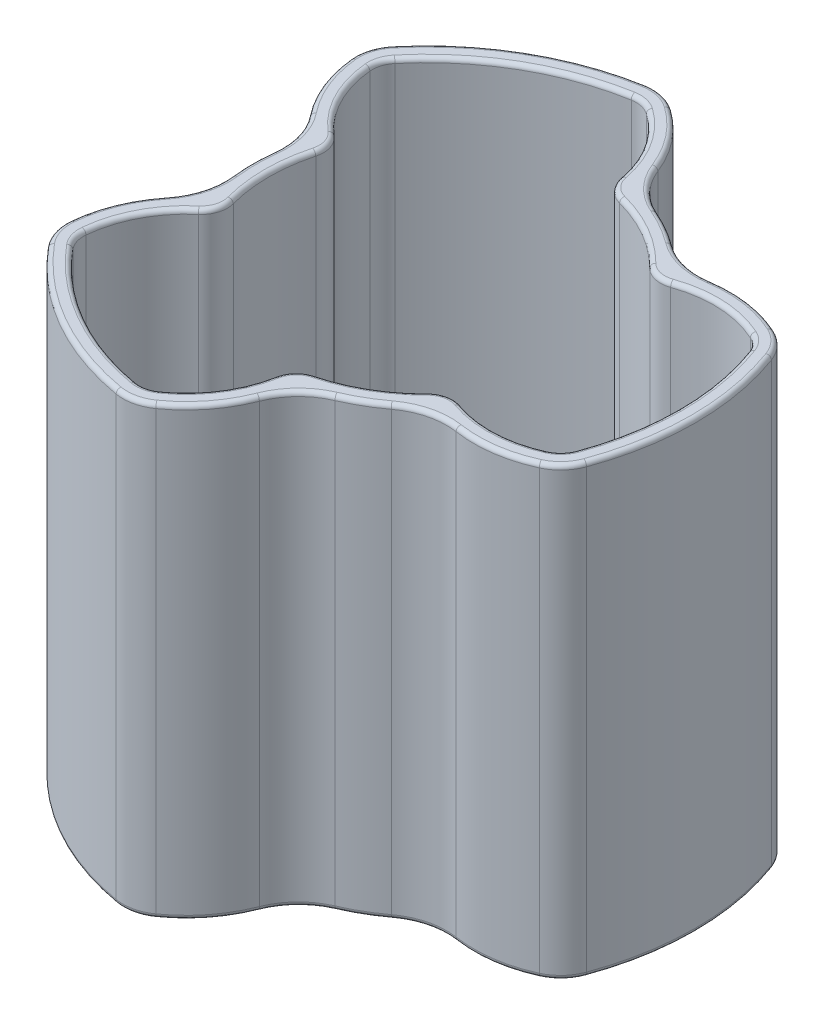
SolidWorks part; units mm, degrees
material "AISI 4340 Stal normalizowana"
ref_plane "Płaszczyzna XY" through (0, 0, 0) normal (0, 0, 1) x (1, 0, 0)
ref_plane "Płaszczyzna XZ" through (0, 0, 0) normal (0, 1, 0) x (1, 0, 0)
ref_plane "Płaszczyzna YZ" through (0, 0, 0) normal (1, 0, 0) x (0, 0, -1)
sketch "Szkic1" plane through (0, 0, 0) normal (0, 1, 0) x (1, 0, 0)
  line L0 (0, 0) -> (-10.15, -17.5803) construction
  line L1 (0, 0) -> (20.3, 0) construction
  arc A0 (28.3884, -12.454) -> (28.3884, 12.454) centre (0, 0) ccw
  arc A1 (26.7972, -11.0864) -> (26.7972, 11.0864) centre (0, 0) ccw
  arc A2 (14.2416, 11.3322) -> (2.6932, 17.9996) centre (0, 0) ccw
  arc A3 (14.7687, 13.7814) -> (4.5507, 19.6807) centre (0, 0) ccw
  circle A4 centre (0, 0) radius 20.3 construction
  arc A5 (26.7972, 11.0864) -> (14.2416, 11.3322) centre (20.3, 0) ccw
  arc A6 (28.3884, 12.454) -> (14.7687, 13.7814) centre (20.3, 0) ccw
  arc A7 (-3.7975, -28.7503) -> (2.6932, -17.9996) centre (-10.15, -17.5803) ccw
  arc A8 (-3.4087, -30.812) -> (4.5507, -19.6807) centre (-10.15, -17.5803) ccw
  arc A9 (-22.9997, 17.6639) -> (-16.9347, 6.6675) centre (-10.15, 17.5803) ccw
  arc A10 (-24.9796, 18.3581) -> (-19.3194, 5.8993) centre (-10.15, 17.5803) ccw
  arc A11 (-16.9347, 6.6675) -> (-16.9347, -6.6675) centre (0, 0) ccw
  arc A12 (-19.3194, 5.8993) -> (-19.3194, -5.8993) centre (0, 0) ccw
  arc A13 (4.5507, -19.6807) -> (14.7687, -13.7814) centre (0, 0) ccw
  arc A14 (2.6932, -17.9996) -> (14.2416, -11.3322) centre (0, 0) ccw
  arc A15 (-3.7975, 28.7503) -> (-22.9997, 17.6639) centre (0, 0) ccw
  arc A16 (-3.4087, 30.812) -> (-24.9796, 18.3581) centre (0, 0) ccw
  arc A17 (-24.9796, -18.3581) -> (-3.4087, -30.812) centre (0, 0) ccw
  arc A18 (-22.9997, -17.6639) -> (-3.7975, -28.7503) centre (0, 0) ccw
  arc A19 (-16.9347, -6.6675) -> (-22.9997, -17.6639) centre (-10.15, -17.5803) ccw
  arc A20 (-19.3194, -5.8993) -> (-24.9796, -18.3581) centre (-10.15, -17.5803) ccw
  arc A21 (4.5507, 19.6807) -> (-3.4087, 30.812) centre (-10.15, 17.5803) ccw
  arc A22 (2.6932, 17.9996) -> (-3.7975, 28.7503) centre (-10.15, 17.5803) ccw
  arc A23 (14.7687, -13.7814) -> (28.3884, -12.454) centre (20.3, 0) ccw
  arc A24 (14.2416, -11.3322) -> (26.7972, -11.0864) centre (20.3, 0) ccw
  point P19 (0, 0)
  dimension "D1" = 58
  dimension "D2" = 2
  dimension "D3" = 36.4
  dimension "D4" = 2
  dimension "D5" = 40.6
  dimension "D6" = 25.7
  dimension "D7" = 2
  dimension "D9" = 120
  dimension "D10" = 20.3
  dimension "D8" = 3
extrude "Dodanie-wyciągnięcie1" add sketch "Szkic1" along normal blind 44.5
extrude "Dodanie-wyciągnięcie2" add sketch "Szkic1<2>" against normal blind 7 contours A23 A0 A6 A3 A21 A16 A10 A12 A20 A17 A8 A13
sketch "Szkic1<2>" plane through (0, 0, 0) normal (0, 1, 0) x (1, 0, 0) same geometry as "Szkic1"
ref_plane "Płaszczyzna2" through (0, -7, 0) normal (0, -1, 0) x (-1, 0, 0)
sketch "Szkic2" plane through (0, -7, 0) normal (0, -1, 0) x (-1, 0, 0)
  line L0 (7.5, -12.9904) -> (0, 0)
  line L1 (0, 0) -> (-15, 0)
  circle A0 centre (0, 0) radius 15 construction
  circle A1 centre (-15, 0) radius 6.5
  circle A2 centre (7.5, 12.9904) radius 6.5
  circle A3 centre (7.5, -12.9904) radius 6.5
  point P12 (0, 0)
  dimension "D1" = 30
  dimension "D2" = 13
  dimension "D4" = 15
  dimension "D5" = 120
  dimension "D3" = 3
extrude "Wytnij-wyciągnięcie1" cut sketch "Szkic2" against normal blind 17 contours A1 | A3 | A2 region at (21.3162, -7, 0) region at (-10.6581, -7, 7.5204) region at (-7.5, -7, -12.9904)
fillet "Zaokrąglenie1" radius 3 12 edges at (14.2416, 22.25, -11.3322) (2.6932, 22.25, -17.9996) (-3.7975, 22.25, -28.7503) (-22.9997, 22.25, -17.6639) (-16.9347, 22.25, -6.6675) (-16.9347, 22.25, 6.6675) (-22.9997, 22.25, 17.6639) (-3.7975, 22.25, 28.7503) (2.6932, 22.25, 17.9996) (14.2416, 22.25, 11.3322) (26.7972, 22.25, 11.0864) (26.7972, 22.25, -11.0864)
fillet "Zaokrąglenie4" [suppressed] radius 2
chamfer "Sfazowanie2" distance 0.5 angle 45 3 edges at (15, 0, 6.5) (-7.5, 0, 19.4904) (-7.5, 0, -6.4904)
fillet "Zaokrąglenie8" radius 5 6 edges at (-24.9796, 18.75, -18.3581) (-24.9796, 18.75, 18.3581) (-3.4087, 18.75, 30.812) (-3.4087, 18.75, -30.812) (28.3884, 18.75, -12.454) (28.3884, 18.75, 12.454)
fillet "Zaokrąglenie9" radius 8 6 edges at (14.7687, 18.75, 13.7814) (4.5507, 18.75, 19.6807) (14.7687, 18.75, -13.7814) (4.5507, 18.75, -19.6807) (-19.3194, 18.75, -5.8993) (-19.3194, 18.75, 5.8993)
fillet "Zaokrąglenie5" radius 0.5 75 edges at (14.3638, 44.5, -12.0244) (20.8889, 44.5, -12.8365) (26.614, 44.5, -10.9872) (29, 44.5, 0) (26.614, 44.5, 10.9872) (20.8889, 44.5, 12.8365) (14.3638, 44.5, 12.0244) (9.1, 44.5, 15.7617) (3.2316, 44.5, 18.4516) (0.6723, 44.5, 24.5086) (-3.7918, 44.5, 28.542) (-14.5, 44.5, 25.1147) (-22.8222, 44.5, 17.5548) (-21.5612, 44.5, 11.6721) (-17.5953, 44.5, 6.4272) (-18.2, 44.5, 0) (-17.5953, 44.5, -6.4272) (-21.5612, 44.5, -11.6721) (-22.8222, 44.5, -17.5548) (-14.5, 44.5, -25.1147) (-3.7918, 44.5, -28.542) (0.6723, 44.5, -24.5086) (3.2316, 44.5, -18.4516) (9.1, 44.5, -15.7617) (10.1, 44.5, 17.4937) (1.548, 44.5, 26.728) (-15.5, 44.5, 26.8468) (-23.9211, 44.5, 12.0234) (-20.2, 44.5, 0) (-23.9211, 44.5, -12.0234) (-15.5, 44.5, -26.8468) (1.548, 44.5, -26.728) (10.1, 44.5, -17.4937) (22.3731, 44.5, -14.7046) (31, 44.5, 0) (22.3731, 44.5, 14.7046) (-3.3509, 44.5, -30.4928) (5.3792, 44.5, -20.3475) (14.9318, 44.5, -14.8323) (28.0829, 44.5, -12.3445) (28.0829, 44.5, 12.3445) (14.9318, 44.5, 14.8323) (5.3792, 44.5, 20.3475) (-3.3509, 44.5, 30.4928) (-24.7321, 44.5, 18.1483) (-20.311, 44.5, 5.5152) (-20.311, 44.5, -5.5152) (-24.7321, 44.5, -18.1483) (-20.311, -7, -5.5152) (-20.2, -7, 0) (-20.311, -7, 5.5152) (-23.9211, -7, 12.0234) (-24.7321, -7, 18.1483) (-15.5, -7, 26.8468) (-3.3509, -7, 30.4928) (1.548, -7, 26.728) (5.3792, -7, 20.3475) (10.1, -7, 17.4937) (14.9318, -7, 14.8323) (22.3731, -7, 14.7046) (28.0829, -7, 12.3445) (31, -7, 0) (28.0829, -7, -12.3445) (22.3731, -7, -14.7046) (14.9318, -7, -14.8323) (10.1, -7, -17.4937) (5.3792, -7, -20.3475) (1.548, -7, -26.728) (-3.3509, -7, -30.4928) (-15.5, -7, -26.8468) (-24.7321, -7, -18.1483) (-23.9211, -7, -12.0234) (15, -7, -6.5) (-7.5, -7, -19.4904) (-7.5, -7, 6.4904)
fillet "Zaokrąglenie10" [suppressed] radius 2
sketch "Szkic3" plane through (0, 0, 0) normal (0, 0, 1) x (1, 0, 0)
  line L0 (0, 0) -> (31, 0)
  line L1 (31, -6.5) -> (31, 44) construction
  line L2 (31, 0) -> (31, 36)
  line L3 (0, 0) -> (0, 70) construction
  line L4 (29, 35) -> (33, 35)
  line L5 (29, 35) -> (29, 37)
  line L6 (29, 37) -> (33, 37)
  line L7 (33, 35) -> (33, 37)
  line L8 (29, 35) -> (33, 37) construction
  line L9 (29, 37) -> (33, 35) construction
  dimension "D1" = 36
  dimension "D2" = 2
  dimension "D3" = 4
  dimension "D4" = 70
revolve "Obrót1" [suppressed] add sketch "Szkic3" angle 360 about L3
sketch "Szkic4" [suppressed] plane through (0, 44.5, 0) normal (0, 1, 0) x (1, 0, 0)
  line L0 (-10.15, 17.5803) -> (0, 0)
  line L1 (0, 0) -> (20.3, 0)
  circle A0 centre (20.3, 0) radius 16.8
  circle A1 centre (-10.15, 17.5803) radius 16.8
  circle A2 centre (-13.1202, -22.7248) radius 16.8
  circle A3 centre (0, 0) radius 27.1035
  circle A4 centre (0, 0) radius 37.1
  arc M29 (-24.9357, 16.1996) -> (-21.7531, 8.3126) centre (-10.15, 17.5803) ccw
  arc M37 (-1.5614, -29.6947) -> (3.6776, -22.995) centre (-10.15, -17.5803) ccw
  arc M45 (26.4971, 13.4951) -> (18.0754, 14.6824) centre (20.3, 0) ccw
  dimension "D1" = 33.6
  dimension "D2" = 33.6
  dimension "D3" = 33.6
  dimension "D7" = 54.207
  dimension "D4" = 20.3
  dimension "D5" = 20.3
  dimension "D6" = 120
extrude "Wytnij-wyciągnięcie2" [suppressed] cut sketch "Szkic4" against normal blind 26 contours A0 A4 A1 A3 M45 | A2 A4 A0 A3 M37 | A1 A4 A2 A3 M29
sketch "Szkic5" plane through (0, -7, 0) normal (0, -1, 0) x (1, 0, 0)
  arc A24 (-2.7181, -28.0632) -> (2.4812, -19.9415) centre (-10.15, -17.5803) ccw
  arc A25 (-4.967, -28.5715) -> (-2.7181, -28.0632) centre (-4.4532, -25.6158) ccw
  arc A26 (-22.2601, -18.5873) -> (-4.967, -28.5715) centre (0, 0) ccw
  arc A27 (-22.9443, -16.3855) -> (-22.2601, -18.5873) centre (-19.9573, -16.6645) ccw
  arc A28 (-18.5105, -7.822) -> (-22.9443, -16.3855) centre (-10.15, -17.5803) ccw
  arc A29 (-18.5105, -7.822) -> (-17.5667, -4.7593) centre (-20.4623, -5.5438) ccw
  arc A30 (-17.5667, 4.7593) -> (-17.5667, -4.7593) centre (0, 0) ccw
  arc A31 (-17.5667, 4.7593) -> (-18.5105, 7.822) centre (-20.4623, 5.5438) ccw
  arc A32 (-22.9443, 16.3855) -> (-18.5105, 7.822) centre (-10.15, 17.5803) ccw
  arc A33 (-22.2601, 18.5873) -> (-22.9443, 16.3855) centre (-19.9573, 16.6645) ccw
  arc A34 (-4.967, 28.5715) -> (-22.2601, 18.5873) centre (0, 0) ccw
  arc A35 (-2.7181, 28.0632) -> (-4.967, 28.5715) centre (-4.4532, 25.6158) ccw
  arc A36 (2.4812, 19.9415) -> (-2.7181, 28.0632) centre (-10.15, 17.5803) ccw
  arc A37 (2.4812, 19.9415) -> (4.6617, 17.5929) centre (5.4301, 20.4928) ccw
  arc A38 (12.905, 12.8336) -> (4.6617, 17.5929) centre (0, 0) ccw
  arc A39 (12.905, 12.8336) -> (16.0293, 12.1195) centre (15.0322, 14.949) ccw
  arc A40 (25.6625, 11.6776) -> (16.0293, 12.1195) centre (20.3, 0) ccw
  arc A41 (27.2271, 9.9842) -> (25.6625, 11.6776) centre (24.4105, 8.9513) ccw
  arc A42 (27.2271, -9.9842) -> (27.2271, 9.9842) centre (0, 0) ccw
  arc A43 (25.6625, -11.6776) -> (27.2271, -9.9842) centre (24.4105, -8.9513) ccw
  arc A44 (16.0293, -12.1195) -> (25.6625, -11.6776) centre (20.3, 0) ccw
  arc A45 (16.0293, -12.1195) -> (12.905, -12.8336) centre (15.0322, -14.949) ccw
  arc A46 (4.6617, -17.5929) -> (12.905, -12.8336) centre (0, 0) ccw
  arc A47 (4.6617, -17.5929) -> (2.4812, -19.9415) centre (5.4301, -20.4928) ccw
  arc A72 (-2.7181, -28.0632) -> (2.4812, -19.9415) centre (-10.15, -17.5803) ccw
  arc A73 (-4.967, -28.5715) -> (-2.7181, -28.0632) centre (-4.4532, -25.6158) ccw
  arc A74 (-22.2601, -18.5873) -> (-4.967, -28.5715) centre (0, 0) ccw
  arc A75 (-22.9443, -16.3855) -> (-22.2601, -18.5873) centre (-19.9573, -16.6645) ccw
  arc A76 (-18.5105, -7.822) -> (-22.9443, -16.3855) centre (-10.15, -17.5803) ccw
  arc A77 (-18.5105, -7.822) -> (-17.5667, -4.7593) centre (-20.4623, -5.5438) ccw
  arc A78 (-17.5667, 4.7593) -> (-17.5667, -4.7593) centre (0, 0) ccw
  arc A79 (-17.5667, 4.7593) -> (-18.5105, 7.822) centre (-20.4623, 5.5438) ccw
  arc A80 (-22.9443, 16.3855) -> (-18.5105, 7.822) centre (-10.15, 17.5803) ccw
  arc A81 (-22.2601, 18.5873) -> (-22.9443, 16.3855) centre (-19.9573, 16.6645) ccw
  arc A82 (-4.967, 28.5715) -> (-22.2601, 18.5873) centre (0, 0) ccw
  arc A83 (-2.7181, 28.0632) -> (-4.967, 28.5715) centre (-4.4532, 25.6158) ccw
  arc A84 (2.4812, 19.9415) -> (-2.7181, 28.0632) centre (-10.15, 17.5803) ccw
  arc A85 (2.4812, 19.9415) -> (4.6617, 17.5929) centre (5.4301, 20.4928) ccw
  arc A86 (12.905, 12.8336) -> (4.6617, 17.5929) centre (0, 0) ccw
  arc A87 (12.905, 12.8336) -> (16.0293, 12.1195) centre (15.0322, 14.949) ccw
  arc A88 (25.6625, 11.6776) -> (16.0293, 12.1195) centre (20.3, 0) ccw
  arc A89 (27.2271, 9.9842) -> (25.6625, 11.6776) centre (24.4105, 8.9513) ccw
  arc A90 (27.2271, -9.9842) -> (27.2271, 9.9842) centre (0, 0) ccw
  arc A91 (25.6625, -11.6776) -> (27.2271, -9.9842) centre (24.4105, -8.9513) ccw
  arc A92 (16.0293, -12.1195) -> (25.6625, -11.6776) centre (20.3, 0) ccw
  arc A93 (16.0293, -12.1195) -> (12.905, -12.8336) centre (15.0322, -14.949) ccw
  arc A94 (4.6617, -17.5929) -> (12.905, -12.8336) centre (0, 0) ccw
  arc A95 (4.6617, -17.5929) -> (2.4812, -19.9415) centre (5.4301, -20.4928) ccw
  dimension "D1" = 0
extrude "Wytnij-wyciągnięcie3" cut sketch "Szkic5" against normal blind 15
